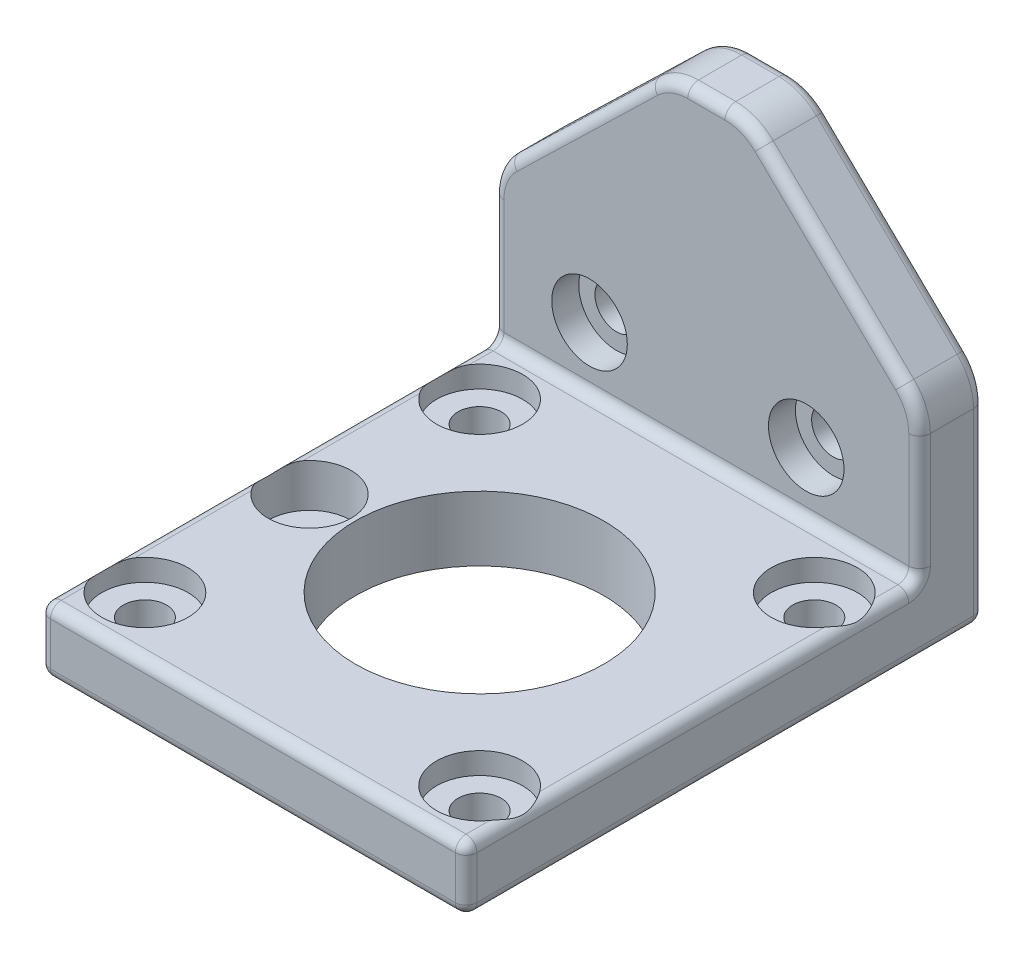
SolidWorks part; units mm, degrees
ref_plane "Front Plane" through (0, 0, 0) normal (0, 0, 1) x (1, 0, 0)
ref_plane "Top Plane" through (0, 0, 0) normal (0, 1, 0) x (1, 0, 0)
ref_plane "Right Plane" through (0, 0, 0) normal (1, 0, 0) x (0, 0, -1)
sketch "Sketch1" plane through (0, 0, 0) normal (0, 1, 0) x (1, 0, 0)
  line L1 (-19.75, 21) -> (19.75, 21)
  line L2 (-19.75, 21) -> (-19.75, -21)
  line L3 (-19.75, -21) -> (19.75, -21)
  line L4 (19.75, 21) -> (19.75, -21)
  line L5 (-19.75, 21) -> (19.75, -21) construction
  line L6 (-19.75, -21) -> (19.75, 21) construction
  point P0 (0, 0)
  dimension "D1" = 39.5
  dimension "D2" = 42
extrude "Boss-Extrude1" add sketch "Sketch1" along normal blind 6
sketch "Sketch3" plane through (0, 6, 0) normal (0, 1, 0) x (1, 0, 0)
  line L0 (0, -15.5) -> (0, 15.5) construction
  line L1 (-15.5, 0) -> (15.5, 0) construction
  line L2 (-15.5, 15.5) -> (15.5, 15.5) construction
  line L3 (15.5, 15.5) -> (15.5, -15.5) construction
  line L4 (15.5, -15.5) -> (-15.5, -15.5) construction
  line L5 (-15.5, -15.5) -> (-15.5, 15.5) construction
  circle A0 centre (-15.5, 15.5) radius 3.9905
  circle A1 centre (15.5, 15.5) radius 3.9905
  circle A2 centre (-15.5, -15.5) radius 3.9905
  circle A3 centre (15.5, -15.5) radius 3.9905
  point P12 (0, 0)
  point P16 (0, 0)
  point P17 (0, 15.5)
  point P20 (15.5, 0)
  dimension "D1" = 7.981
  dimension "D2" = 31
  dimension "D3" = 31
extrude "Cut-Extrude1" cut sketch "Sketch3" against normal blind 2
sketch "Sketch4" plane through (0, 6, 0) normal (0, 1, 0) x (1, 0, 0)
  circle A0 centre (0, 0) radius 11.5
  circle A1 centre (15.5, 15.5) radius 2
  circle A2 centre (-15.5, 15.5) radius 2
  circle A3 centre (-15.5, -15.5) radius 2
  circle A4 centre (15.5, -15.5) radius 2
  dimension "D1" = 4
  dimension "D2" = 23
extrude "Cut-Extrude2" cut sketch "Sketch4" against normal through all
sketch "Sketch5" plane through (0, 0, -21) normal (0, 0, -1) x (-1, 0, 0)
  line L0 (0, 9.875) -> (0, 19.75) construction
  line L2 (-19.75, 19.75) -> (-19.75, 0)
  line L3 (-19.75, 0) -> (19.75, 0)
  line L4 (19.75, 19.75) -> (19.75, 0)
  line L5 (-19.75, 19.75) -> (19.75, 0) construction
  line L6 (-19.75, 0) -> (19.75, 19.75) construction
  line L7 (-3.75, 35.25) -> (3.75, 35.25)
  line L13 (3.75, 35.25) -> (19.75, 19.75)
  line L14 (-3.75, 35.25) -> (-19.75, 19.75)
  point P0 (0, 9.875)
  point P6 (0, 27.5)
  dimension "D1" = 35.25
  dimension "D2" = 19.75
  dimension "D3" = 16
  dimension "D4" = 16
  dimension "D5" = 15.5
extrude "Boss-Extrude2" add sketch "Sketch5" along normal blind 6
sketch "Sketch6" plane through (0, 0, -21) normal (0, 0, 1) x (1, 0, 0)
  line L0 (-10.82, 11.75) -> (9.25, 11.75) construction
  line L1 (19.75, 6.7748) -> (-0.785, 6.7748) construction
  line L2 (19.75, 19.75) -> (19.75, 6) construction
  line L3 (-0.785, 6.7748) -> (-0.785, 11.75) construction
  circle A0 centre (-10.82, 11.75) radius 3.5
  circle A1 centre (9.25, 11.75) radius 3.5
  dimension "D1" = 7
  dimension "D2" = 7
  dimension "D3" = 20.535
  dimension "D4" = 20.07
  dimension "D5" = 11.75
extrude "Cut-Extrude3" cut sketch "Sketch6" against normal blind 2.5
sketch "Sketch7" plane through (0, 0, -21) normal (0, 0, 1) x (1, 0, 0)
  circle A0 centre (-10.82, 11.75) radius 2
  circle A1 centre (9.25, 11.75) radius 2
  dimension "D1" = 4
extrude "Cut-Extrude4" cut sketch "Sketch7" against normal through all
fillet "Fillet1" radius 5 4 edges at (19.75, 19.75, -24) (3.75, 35.25, -24) (-3.75, 35.25, -24) (-19.75, 19.75, -24)
sketch "Sketch8" plane through (0, 6, 0) normal (0, 1, 0) x (1, 0, 0)
  line L0 (0, 0) -> (-15.75, 0) construction
  circle A0 centre (-15.75, 0) radius 3.8413
  dimension "D1" = 7.6825
  dimension "D2" = 15.75
extrude "Cut-Extrude5" cut sketch "Sketch8" against normal blind 4
fillet "Fillet2" radius 1 28 edges at (0, 35.25, -21) (3.602, 34.8844, -21) (-3.602, 34.8844, -21) (11.7166, 27.5323, -21) (-11.7166, 27.5323, -21) (19.3541, 19.5823, -21) (-19.3541, 19.5823, -21) (19.75, 11.8161, -21) (-19.75, 11.8161, -21) (-19.75, 8.8161, -27) (-19.3541, 19.5823, -27) (-11.7166, 27.5323, -27) (-3.602, 34.8844, -27) (19.75, 8.8161, -27) (19.3541, 19.5823, -27) (11.7166, 27.5323, -27) (3.602, 34.8844, -27) (0, 0, -27) (0, 35.25, -27) (0, 6, -21) (0, 0, 21) (0, 6, 21) (19.75, 0, -3) (19.75, 6, 0) (-19.75, 0, -3) (-19.75, 6, 0) (-19.75, 3, 21) (19.75, 3, 21)
